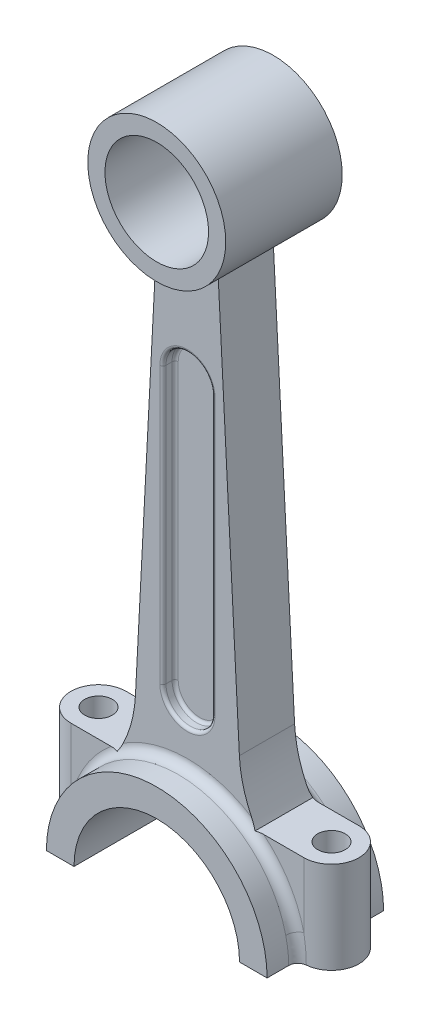
SolidWorks part; units mm, degrees
ref_plane "Front Plane" through (0, 0, 0) normal (0, 0, 1) x (1, 0, 0)
ref_plane "Top Plane" through (0, 0, 0) normal (0, 1, 0) x (1, 0, 0)
ref_plane "Right Plane" through (0, 0, 0) normal (1, 0, 0) x (0, 0, -1)
sketch "Sketch1" plane through (0, 0, 0) normal (0, 0, 1) x (1, 0, 0)
  line L0 (-36, -201.2) -> (36, -201.2)
  line L1 (-10, -20.1556) -> (-17.8497, -169.9368)
  line L2 (10, -20.1556) -> (17.8497, -169.9368)
  circle A0 centre (0, 0) radius 22.5
  circle A1 centre (0, 0) radius 16.9
  arc A2 (36, -201.2) -> (-36, -201.2) centre (0, -201.2) ccw
  arc A3 (27, -201.2) -> (-27, -201.2) centre (0, -201.2) ccw
  dimension "D1" = 33.8
  dimension "D2" = 45
  dimension "D3" = 54
  dimension "D4" = 72
  dimension "D5" = 201.2
  dimension "D6" = 20
  dimension "D7" = 6
extrude "Boss-Extrude1" add sketch "Sketch1" along normal mid plane 38 contours A1 A0 | A2 A3 region at (-30.4373, -183.5292, 0) region at (-11.5231, 18.5805, 0)
extrude "Boss-Extrude2" add sketch "Sketch1<5>" along normal mid plane 18 contours A2 L2 A0 L1 region at (0, -100.8455, 0)
sketch "Sketch1<5>" plane through (0, 0, 0) normal (0, 0, 1) x (1, 0, 0) same geometry as "Sketch1"
sketch "Sketch2" plane through (0, 0, 9) normal (0, 0, 1) x (1, 0, 0)
  line L1 (0, -145.6) -> (0, -55.6) construction
  line L3 (-8, -145.6) -> (-8, -55.6)
  line L4 (8, -145.6) -> (8, -55.6)
  arc A0 (-8, -145.6) -> (8, -145.6) centre (0, -145.6) ccw
  arc A1 (8, -55.6) -> (-8, -55.6) centre (0, -55.6) ccw
  point P6 (0, -100.6)
  dimension "D1" = 8
  dimension "D2" = 90
extrude "Cut-Extrude1" cut sketch "Sketch2" against normal blind 4
mirror "Mirror1" about plane through (0, 0, 0) normal (0, 0, 1) of "Cut-Extrude1"
fillet "Fillet1" radius 1 16 edges at (8, -100.6, -9) (0, -153.6, -9) (-8, -100.6, -9) (8, -100.6, -5) (0, -153.6, -5) (-8, -100.6, -5) (8, -100.6, 5) (0, -153.6, 5) (-8, -100.6, 5) (8, -100.6, 9) (0, -153.6, 9) (-8, -100.6, 9) (0, -47.6, -9) (0, -47.6, -5) (0, -47.6, 5) (0, -47.6, 9)
fillet "Fillet3" radius 40 2 edges at (-17.8497, -169.9368, 0) (17.8497, -169.9368, 0)
ref_plane "Plane2" through (0, -171.2, 0) normal (0, 1, 0) x (1, 0, 0)
sketch "Sketch4" plane through (0, -171.2, 0) normal (0, 1, 0) x (1, 0, 0)
  line L0 (-38, 0) -> (38, 0) construction
  line L1 (-27, -19) -> (27, -19) construction
  line L2 (-38, 9) -> (38, 9)
  line L3 (-38, -9) -> (38, -9)
  line L4 (-27, -19) -> (27, -19)
  arc A0 (-38, 9) -> (-38, -9) centre (-38, 0) ccw
  arc A1 (38, -9) -> (38, 9) centre (38, 0) ccw
  point P4 (0, 0)
extrude "Boss-Extrude4" add sketch "Sketch4" against normal up to surface (30 mm away) contours L3 A1 L2 A0 | L3 A1 L2 A0 region at (0, -171.2, 0) up to face at (31.5, -201.2, 0)
sketch "Sketch5" plane through (0, 0, 9) normal (0, 0, 1) x (1, 0, 0)
  line L1 (-27, -201.2) -> (27, -201.2)
  line L2 (-27, -201.2) -> (27, -201.2)
  arc A1 (27, -201.2) -> (-27, -201.2) centre (0, -201.2) ccw
  arc A2 (27, -201.2) -> (-27, -201.2) centre (0, -201.2) ccw
  dimension "D1" = 0
extrude "Cut-Extrude2" cut sketch "Sketch5" against normal through all
sketch "Sketch7" plane through (0, -171.2, 0) normal (0, 1, 0) x (1, 0, 0)
  circle A0 centre (-38, 0) radius 4.5
  circle A1 centre (38, 0) radius 4.5
  point P3 (0, 0)
extrude "Cut-Extrude3" cut sketch "Sketch7" against normal through all
fillet "Fillet6" radius 3 2 edges at (0, -165.2, -9) (0, -165.2, 9)
